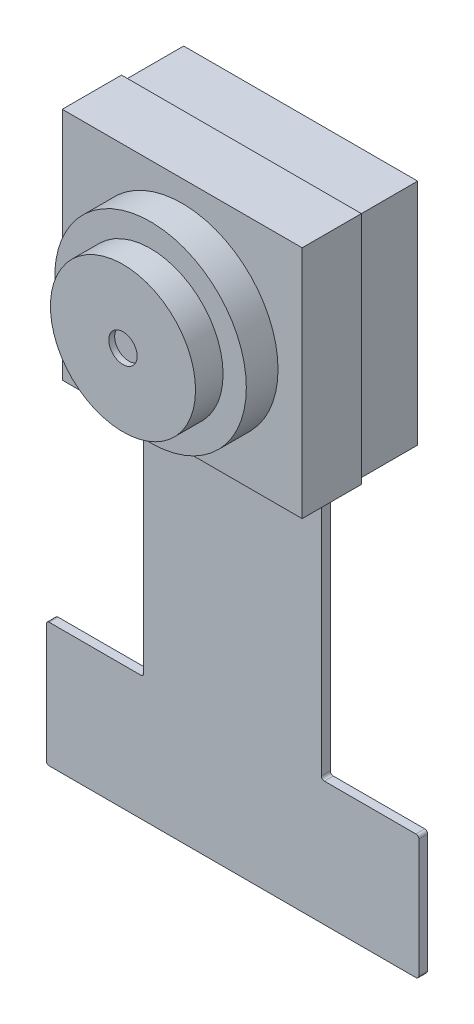
SolidWorks part; units mm, degrees
ref_plane "Front Plane" through (0, 0, 0) normal (0, 0, 1) x (1, 0, 0)
ref_plane "Top Plane" through (0, 0, 0) normal (0, 1, 0) x (1, 0, 0)
ref_plane "Right Plane" through (0, 0, 0) normal (1, 0, 0) x (0, 0, -1)
sketch "Sketch1" plane through (0, 0, 0) normal (0, 0, 1) x (1, 0, 0)
  line L1 (4.05, -3.96) -> (-4.05, -3.96)
  line L2 (4.05, -3.96) -> (4.05, 3.96)
  line L3 (4.05, 3.96) -> (-4.05, 3.96)
  line L4 (-4.05, -3.96) -> (-4.05, 3.96)
  line L5 (4.05, -3.96) -> (-4.05, 3.96) construction
  line L6 (4.05, 3.96) -> (-4.05, -3.96) construction
  point P0 (0, 0)
  dimension "D1" = 8.1
  dimension "D2" = 7.92
extrude "Boss-Extrude1" add sketch "Sketch1" along normal blind 6
sketch "Sketch2" plane through (0, 0, 6) normal (0, 0, 1) x (1, 0, 0)
  line L1 (-4.05, 3.96) -> (4.05, 3.96)
  line L2 (-4.05, 3.96) -> (-4.05, -3.96)
  line L3 (-4.05, -3.96) -> (4.05, -3.96)
  line L4 (4.05, 3.96) -> (4.05, -3.96)
  circle A0 centre (0, 0) radius 3.235
  dimension "D1" = 6.47
extrude "Cut-Extrude1" cut sketch "Sketch2" against normal blind 2
sketch "Sketch3" plane through (0, 0, 6) normal (0, 0, 1) x (1, 0, 0)
  circle A0 centre (0, 0) radius 2.45
  circle A1 centre (0, 0) radius 3.235
  dimension "D1" = 4.9
extrude "Cut-Extrude2" cut sketch "Sketch3" against normal blind 0.93
sketch "Sketch4" plane through (0, 0, 6) normal (0, 0, 1) x (1, 0, 0)
  circle A0 centre (0, 0) radius 0.48
  dimension "D1" = 0.96
extrude "Cut-Extrude3" cut sketch "Sketch4" against normal blind 0.2
sketch "Sketch5" plane through (0, 0, 0) normal (0, 0, -1) x (-1, 0, 0)
  line L1 (4.05, -3.96) -> (-4.05, -3.96)
  line L2 (4.05, -3.96) -> (4.05, 3.96)
  line L3 (4.05, 3.96) -> (-4.05, 3.96)
  line L4 (-4.05, -3.96) -> (-4.05, 3.96)
  line L5 (4.05, -3.96) -> (-4.05, 3.96) construction
  line L6 (4.05, 3.96) -> (-4.05, -3.96) construction
  line L7 (3.95, -3.86) -> (-3.95, -3.86)
  line L8 (3.95, -3.86) -> (3.95, 3.86)
  line L9 (3.95, 3.86) -> (-3.95, 3.86)
  line L10 (-3.95, -3.86) -> (-3.95, 3.86)
  line L11 (3.95, -3.86) -> (-3.95, 3.86) construction
  line L12 (3.95, 3.86) -> (-3.95, -3.86) construction
  point P0 (0, 0)
  point P5 (0, 0)
  dimension "D1" = 0.1
  dimension "D2" = 0.1
extrude "Cut-Extrude4" cut sketch "Sketch5" against normal blind 2
sketch "Sketch6" plane through (0, 0, 2) normal (0, 0, -1) x (-1, 0, 0)
  line L0 (-4.05, -3.96) -> (4.05, -3.96) construction
  line L1 (3, -17.16) -> (-3, -17.16)
  line L2 (3, -17.16) -> (3, -3.96) construction
  line L3 (3, -3.96) -> (-3, -3.96)
  line L4 (-3, -17.16) -> (-3, -3.96) construction
  line L5 (3, -17.16) -> (-3, -3.96) construction
  line L6 (3, -3.96) -> (-3, -17.16) construction
  line L7 (0, 0) -> (0, -17.16) construction
  line L8 (0, -12.96) -> (0, -17.16) construction
  line L9 (-6.29, -12.96) -> (6.29, -12.96) construction
  line L10 (-6.29, -12.96) -> (-6.29, -17.16)
  line L11 (-6.29, -17.16) -> (6.29, -17.16)
  line L12 (6.29, -12.96) -> (6.29, -17.16)
  line L13 (-6.29, -12.96) -> (-3, -12.96)
  line L14 (-3, -12.96) -> (-3, -3.96)
  line L15 (6.29, -12.96) -> (3, -12.96)
  line L16 (3, -3.96) -> (3, -12.96)
  point P0 (0, -10.56)
  line M6 (-4.05, -3.96) -> (4.05, -3.96)
  dimension "D1" = 6
  dimension "D2" = 13.2
  dimension "D3" = 12.58
  dimension "D4" = 4.2
extrude "Boss-Extrude2" add sketch "Sketch6" against normal blind 0.3 contours L16 L14 L13 L10 L11 L1 L12 L15 M6 region at (0, -11.724, 2)
sketch "Sketch7" plane through (0, 0, 2) normal (0, 0, -1) x (-1, 0, 0)
  line L1 (-6.29, -12.96) -> (-6.29, -17.16) construction
  line L2 (6.29, -12.96) -> (6.29, -17.16) construction
  line L3 (-6.29, -14.61) -> (6.29, -14.61)
  line L4 (-6.29, -17.16) -> (6.29, -17.16) construction
  line L5 (-5.95, -14.62) -> (-5.55, -14.62)
  line L6 (-5.95, -14.62) -> (-5.95, -17.16)
  line L7 (-5.95, -17.16) -> (-5.55, -17.16)
  line L8 (-5.55, -14.62) -> (-5.55, -17.16)
  line L9 (-5.45, -14.62) -> (-5.05, -14.62)
  line L10 (-5.45, -14.62) -> (-5.45, -17.16)
  line L11 (-5.45, -17.16) -> (-5.05, -17.16)
  line L12 (-5.05, -14.62) -> (-5.05, -17.16)
  line L13 (-4.95, -14.62) -> (-4.55, -14.62)
  line L14 (-4.95, -14.62) -> (-4.95, -17.16)
  line L15 (-4.95, -17.16) -> (-4.55, -17.16)
  line L16 (-4.55, -14.62) -> (-4.55, -17.16)
  line L17 (-4.45, -14.62) -> (-4.05, -14.62)
  line L18 (-4.45, -14.62) -> (-4.45, -17.16)
  line L19 (-4.45, -17.16) -> (-4.05, -17.16)
  line L20 (-4.05, -14.62) -> (-4.05, -17.16)
  line L21 (-3.95, -14.62) -> (-3.55, -14.62)
  line L22 (-3.95, -14.62) -> (-3.95, -17.16)
  line L23 (-3.95, -17.16) -> (-3.55, -17.16)
  line L24 (-3.55, -14.62) -> (-3.55, -17.16)
  line L25 (-3.45, -14.62) -> (-3.05, -14.62)
  line L26 (-3.45, -14.62) -> (-3.45, -17.16)
  line L27 (-3.45, -17.16) -> (-3.05, -17.16)
  line L28 (-3.05, -14.62) -> (-3.05, -17.16)
  line L29 (-2.95, -14.62) -> (-2.55, -14.62)
  line L30 (-2.95, -14.62) -> (-2.95, -17.16)
  line L31 (-2.95, -17.16) -> (-2.55, -17.16)
  line L32 (-2.55, -14.62) -> (-2.55, -17.16)
  line L33 (-2.45, -14.62) -> (-2.05, -14.62)
  line L34 (-2.45, -14.62) -> (-2.45, -17.16)
  line L35 (-2.45, -17.16) -> (-2.05, -17.16)
  line L36 (-2.05, -14.62) -> (-2.05, -17.16)
  line L37 (-1.95, -14.62) -> (-1.55, -14.62)
  line L38 (-1.95, -14.62) -> (-1.95, -17.16)
  line L39 (-1.95, -17.16) -> (-1.55, -17.16)
  line L40 (-1.55, -14.62) -> (-1.55, -17.16)
  line L41 (-1.45, -14.62) -> (-1.05, -14.62)
  line L42 (-1.45, -14.62) -> (-1.45, -17.16)
  line L43 (-1.45, -17.16) -> (-1.05, -17.16)
  line L44 (-1.05, -14.62) -> (-1.05, -17.16)
  line L45 (-0.95, -14.62) -> (-0.55, -14.62)
  line L46 (-0.95, -14.62) -> (-0.95, -17.16)
  line L47 (-0.95, -17.16) -> (-0.55, -17.16)
  line L48 (-0.55, -14.62) -> (-0.55, -17.16)
  line L49 (-0.45, -14.62) -> (-0.05, -14.62)
  line L50 (-0.45, -14.62) -> (-0.45, -17.16)
  line L51 (-0.45, -17.16) -> (-0.05, -17.16)
  line L52 (-0.05, -14.62) -> (-0.05, -17.16)
  line L53 (0.05, -14.62) -> (0.45, -14.62)
  line L54 (0.05, -14.62) -> (0.05, -17.16)
  line L55 (0.05, -17.16) -> (0.45, -17.16)
  line L56 (0.45, -14.62) -> (0.45, -17.16)
  line L57 (0.55, -14.62) -> (0.95, -14.62)
  line L58 (0.55, -14.62) -> (0.55, -17.16)
  line L59 (0.55, -17.16) -> (0.95, -17.16)
  line L60 (0.95, -14.62) -> (0.95, -17.16)
  line L61 (1.05, -14.62) -> (1.45, -14.62)
  line L62 (1.05, -14.62) -> (1.05, -17.16)
  line L63 (1.05, -17.16) -> (1.45, -17.16)
  line L64 (1.45, -14.62) -> (1.45, -17.16)
  line L65 (1.55, -14.62) -> (1.95, -14.62)
  line L66 (1.55, -14.62) -> (1.55, -17.16)
  line L67 (1.55, -17.16) -> (1.95, -17.16)
  line L68 (1.95, -14.62) -> (1.95, -17.16)
  line L69 (2.05, -14.62) -> (2.45, -14.62)
  line L70 (2.05, -14.62) -> (2.05, -17.16)
  line L71 (2.05, -17.16) -> (2.45, -17.16)
  line L72 (2.45, -14.62) -> (2.45, -17.16)
  line L73 (2.55, -14.62) -> (2.95, -14.62)
  line L74 (2.55, -14.62) -> (2.55, -17.16)
  line L75 (2.55, -17.16) -> (2.95, -17.16)
  line L76 (2.95, -14.62) -> (2.95, -17.16)
  line L77 (3.05, -14.62) -> (3.45, -14.62)
  line L78 (3.05, -14.62) -> (3.05, -17.16)
  line L79 (3.05, -17.16) -> (3.45, -17.16)
  line L80 (3.45, -14.62) -> (3.45, -17.16)
  line L81 (3.55, -14.62) -> (3.95, -14.62)
  line L82 (3.55, -14.62) -> (3.55, -17.16)
  line L83 (3.55, -17.16) -> (3.95, -17.16)
  line L84 (3.95, -14.62) -> (3.95, -17.16)
  line L85 (4.05, -14.62) -> (4.45, -14.62)
  line L86 (4.05, -14.62) -> (4.05, -17.16)
  line L87 (4.05, -17.16) -> (4.45, -17.16)
  line L88 (4.45, -14.62) -> (4.45, -17.16)
  line L89 (4.55, -14.62) -> (4.95, -14.62)
  line L90 (4.55, -14.62) -> (4.55, -17.16)
  line L91 (4.55, -17.16) -> (4.95, -17.16)
  line L92 (4.95, -14.62) -> (4.95, -17.16)
  line L93 (5.05, -14.62) -> (5.45, -14.62)
  line L94 (5.05, -14.62) -> (5.05, -17.16)
  line L95 (5.05, -17.16) -> (5.45, -17.16)
  line L96 (5.45, -14.62) -> (5.45, -17.16)
  line L97 (5.55, -14.62) -> (5.95, -14.62)
  line L98 (5.55, -14.62) -> (5.55, -17.16)
  line L99 (5.55, -17.16) -> (5.95, -17.16)
  line L100 (5.95, -14.62) -> (5.95, -17.16)
  line L101 (-6.29, -14.61) -> (6.29, -14.61)
  line L102 (-6.29, -14.61) -> (-6.29, -17.16)
  line L103 (-6.29, -17.16) -> (6.29, -17.16)
  line L104 (6.29, -14.61) -> (6.29, -17.16)
  line M105 (-6.29, -12.96) -> (-6.29, -17.16)
  line M106 (-6.29, -17.16) -> (6.29, -17.16)
  line M107 (6.29, -17.16) -> (6.29, -12.96)
  dimension "D1" = 0.34
  dimension "D2" = 0.4
  dimension "D3" = 24
  dimension "D4" = 0.01
extrude "Cut-Extrude5" cut sketch "Sketch7" against normal blind 0.01 contours L97 L100 L3 L6 L5 L8 L10 L9 L12 L14 L13 L16 L18 L17 L20 L22 L21 L24 L26 L25 L28 L30 L29 L32 L34 L33 L36 L38 L37 L40 L42 L41 L44 L46 L45 L48 M106 M107 M105 region at (0, -15.8692, 2)
fillet "Fillet1" radius 0.1 6 edges at (-6.29, -17.16, 2.155) (6.29, -17.16, 2.155) (3, -12.96, 2.15) (-3, -12.96, 2.15) (-6.29, -12.96, 2.15) (6.29, -12.96, 2.15)
